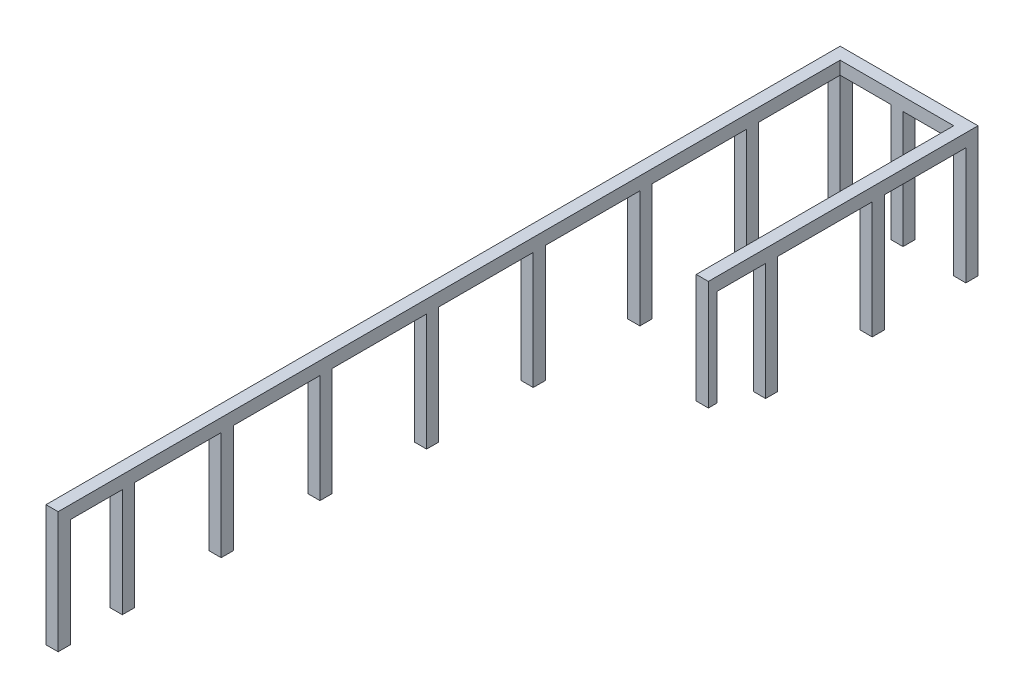
SolidWorks part; units mm, degrees
ref_plane "前视基准面" through (0, 0, 0) normal (0, 0, 1) x (1, 0, 0)
ref_plane "上视基准面" through (0, 0, 0) normal (0, 1, 0) x (1, 0, 0)
ref_plane "右视基准面" through (0, 0, 0) normal (1, 0, 0) x (0, 0, -1)
other "Configuration Table"
sketch "草图1" plane through (0, 0, 0) normal (0, 1, 0) x (1, 0, 0)
  line L13 (1.6, -1.6) -> (4.4, -1.6)
  line L14 (1.6, -1.6) -> (1.6, -4.4)
  line L15 (1.6, -4.4) -> (4.4, -4.4)
  line L16 (4.4, -1.6) -> (4.4, -4.4)
  line L17 (16.1, -1.6) -> (18.9, -1.6)
  line L18 (16.1, -1.6) -> (16.1, -4.4)
  line L19 (16.1, -4.4) -> (18.9, -4.4)
  line L20 (18.9, -1.6) -> (18.9, -4.4)
  line L21 (30.6, -1.6) -> (33.4, -1.6)
  line L22 (30.6, -1.6) -> (30.6, -4.4)
  line L23 (30.6, -4.4) -> (33.4, -4.4)
  line L24 (33.4, -1.6) -> (33.4, -4.4)
  line L25 (4.4, -1.6) -> (16.1, -1.6)
  line L26 (4.4, -1.6) -> (4.4, -4.4)
  line L27 (4.4, -4.4) -> (16.1, -4.4)
  line L28 (16.1, -1.6) -> (16.1, -4.4)
  line L29 (18.9, -1.6) -> (30.6, -1.6)
  line L30 (18.9, -1.6) -> (18.9, -4.4)
  line L31 (18.9, -4.4) -> (30.6, -4.4)
  line L32 (30.6, -1.6) -> (30.6, -4.4)
  line L33 (1.6, -23.2) -> (4.4, -23.2)
  line L34 (1.6, -23.2) -> (1.6, -26)
  line L35 (1.6, -26) -> (4.4, -26)
  line L36 (4.4, -23.2) -> (4.4, -26)
  line L37 (1.6, -47.8) -> (4.4, -47.8)
  line L38 (1.6, -47.8) -> (1.6, -50.6)
  line L39 (1.6, -50.6) -> (4.4, -50.6)
  line L40 (4.4, -47.8) -> (4.4, -50.6)
  line L41 (1.6, -72.4) -> (4.4, -72.4)
  line L42 (1.6, -72.4) -> (1.6, -75.2)
  line L43 (1.6, -75.2) -> (4.4, -75.2)
  line L44 (4.4, -72.4) -> (4.4, -75.2)
  line L45 (1.6, -97) -> (4.4, -97)
  line L46 (1.6, -97) -> (1.6, -99.8)
  line L47 (1.6, -99.8) -> (4.4, -99.8)
  line L48 (4.4, -97) -> (4.4, -99.8)
  line L53 (30.6, -47.8) -> (33.4, -47.8)
  line L54 (30.6, -47.8) -> (30.6, -50.6)
  line L55 (30.6, -50.6) -> (33.4, -50.6)
  line L56 (33.4, -47.8) -> (33.4, -50.6)
  line L57 (30.6, -23.2) -> (33.4, -23.2)
  line L58 (30.6, -23.2) -> (30.6, -26)
  line L59 (30.6, -26) -> (33.4, -26)
  line L60 (33.4, -23.2) -> (33.4, -26)
  line L61 (1.6, -4.4) -> (4.4, -4.4)
  line L62 (1.6, -4.4) -> (1.6, -23.2)
  line L63 (1.6, -23.2) -> (4.4, -23.2)
  line L64 (4.4, -4.4) -> (4.4, -23.2)
  line L65 (1.6, -26) -> (4.4, -26)
  line L66 (1.6, -26) -> (1.6, -47.8)
  line L67 (1.6, -47.8) -> (4.4, -47.8)
  line L68 (4.4, -26) -> (4.4, -47.8)
  line L69 (4.4, -72.4) -> (1.6, -72.4)
  line L70 (4.4, -72.4) -> (4.4, -50.6)
  line L71 (4.4, -50.6) -> (1.6, -50.6)
  line L72 (1.6, -72.4) -> (1.6, -50.6)
  line L73 (1.6, -75.2) -> (4.4, -75.2)
  line L74 (1.6, -75.2) -> (1.6, -97)
  line L75 (1.6, -97) -> (4.4, -97)
  line L76 (4.4, -75.2) -> (4.4, -97)
  line L77 (1.6, -99.8) -> (4.4, -99.8)
  line L78 (1.6, -99.8) -> (1.6, -121.6)
  line L79 (1.6, -121.6) -> (4.4, -121.6)
  line L80 (4.4, -99.8) -> (4.4, -121.6)
  line L81 (1.6, -121.6) -> (4.4, -121.6)
  line L82 (1.6, -121.6) -> (1.6, -124.4)
  line L83 (1.6, -124.4) -> (4.4, -124.4)
  line L84 (4.4, -121.6) -> (4.4, -124.4)
  line L85 (1.6, -124.4) -> (4.4, -124.4)
  line L86 (1.6, -124.4) -> (1.6, -144.4)
  line L87 (1.6, -144.4) -> (4.4, -144.4)
  line L88 (4.4, -124.4) -> (4.4, -144.4)
  line L89 (4.4, -144.4) -> (1.6, -144.4)
  line L90 (4.4, -144.4) -> (4.4, -147.2)
  line L91 (4.4, -147.2) -> (1.6, -147.2)
  line L92 (1.6, -144.4) -> (1.6, -147.2)
  line L93 (1.6, -147.2) -> (4.4, -147.2)
  line L94 (1.6, -147.2) -> (1.6, -167.2)
  line L95 (1.6, -167.2) -> (4.4, -167.2)
  line L96 (4.4, -147.2) -> (4.4, -167.2)
  line L97 (4.4, -167.2) -> (1.6, -167.2)
  line L98 (4.4, -167.2) -> (4.4, -170)
  line L99 (4.4, -170) -> (1.6, -170)
  line L100 (1.6, -167.2) -> (1.6, -170)
  line L101 (1.6, -170) -> (4.4, -170)
  line L102 (1.6, -170) -> (1.6, -182)
  line L103 (1.6, -182) -> (4.4, -182)
  line L104 (4.4, -170) -> (4.4, -182)
  line L105 (1.6, -182) -> (4.4, -182)
  line L106 (1.6, -182) -> (1.6, -184.8)
  line L107 (1.6, -184.8) -> (4.4, -184.8)
  line L108 (4.4, -182) -> (4.4, -184.8)
  line L109 (30.6, -4.4) -> (33.4, -4.4)
  line L110 (30.6, -4.4) -> (30.6, -23.2)
  line L111 (30.6, -23.2) -> (33.4, -23.2)
  line L112 (33.4, -4.4) -> (33.4, -23.2)
  line L113 (33.4, -26) -> (30.6, -26)
  line L114 (33.4, -26) -> (33.4, -47.8)
  line L115 (33.4, -47.8) -> (30.6, -47.8)
  line L116 (30.6, -26) -> (30.6, -47.8)
  point P50 (3, -72.4)
  dimension "D3" = 1.6
  dimension "D4" = 11.7
  dimension "D5" = 11.7
  dimension "D1" = 2.8
  dimension "D2" = 1.6
  dimension "D6" = 18.8
  dimension "D7" = 21.8
  dimension "D8" = 21.8
  dimension "D9" = 21.8
  dimension "D10" = 21.8
  dimension "D11" = 20
  dimension "D12" = 20
  dimension "D13" = 12
extrude "凸台-拉伸1" add sketch "草图1" along normal blind 30 contours L108 L103 L106 L107 | L95 L100 L99 L98 | L87 L92 L91 L90 | L84 L79 L82 L83 | L48 L45 L46 L47 | L44 L41 L42 L43 | L40 L37 L38 L39 | L56 L53 L54 L55 | L60 L57 L58 L59 | L36 L33 L34 L35 | L24 L21 L22 L23 | L20 L17 L18 L19 | L16 L13 L14 L15
extrude "凸台-拉伸2" add sketch "草图1<6>" against normal blind 3 from surface contours L108 | L104 L99 L102 L103 | L96 L91 L94 L95 | L88 L83 L86 L87 | L80 L47 L78 L79 | L76 L43 L74 L45 | L72 L41 L70 L39 | L68 L35 L66 L37 | L64 L15 L62 L33 | L16 L27 L18 L25 | L20 L31 L22 L29 | L112 L23 L110 L57 | L59 L116 L53 L114 | L55 region at (10.25, 0, 3) region at (3, 0, 13.8) region at (24.75, 0, 3) region at (3, 0, 36.9) region at (32, 0, 13.8) region at (3, 0, 61.5) region at (32, 0, 36.9) region at (3, 0, 86.1) region at (3, 0, 110.7) region at (3, 0, 134.4) region at (3, 0, 157.2) region at (3, 0, 176) starting at face at (3, 30, 49.2)
sketch "草图1<6>" plane through (0, 0, 0) normal (0, 1, 0) x (1, 0, 0) same geometry as "草图1"
sketch "草图2" plane through (1.6, 0, 0) normal (-1, 0, 0) x (0, 0, 1)
  line L0 (184.8, 30) -> (184.8, 0) construction
  line L1 (184.8, 0) -> (121.6, 0)
  line L2 (184.8, 0) -> (184.8, 2)
  line L3 (184.8, 2) -> (121.6, 2)
  line L4 (121.6, 0) -> (121.6, 2)
  line L5 (121.6, 27) -> (121.6, 0) construction
  line L6 (121.6, 0) -> (124.4, 0) construction
  dimension "D1" = 2
extrude "切除-拉伸1" cut sketch "草图2" against normal through all
sketch "草图3" plane through (33.4, 0, 0) normal (1, 0, 0) x (0, 0, -1)
  line L0 (-4.4, 30) -> (-184.8, 30) construction
  line L1 (-61.8, 4.7) -> (-63.8, 4.7)
  line L2 (-61.8, 4.7) -> (-61.8, 30)
  line L3 (-61.8, 30) -> (-63.8, 30)
  line L4 (-63.8, 4.7) -> (-63.8, 30)
  line L5 (-50.6, 27) -> (-72.4, 27) construction
  line L6 (-61.8, 30) -> (-50.6, 30)
  line L7 (-61.8, 30) -> (-61.8, 27)
  line L8 (-61.8, 27) -> (-50.6, 27)
  line L9 (-50.6, 30) -> (-50.6, 27)
  line L10 (-50.6, 30) -> (-50.6, 0) construction
  point P13 (-61.8, 4.5)
  dimension "D1" = 2
  dimension "D2" = 11.2
  dimension "D3" = 25.3
extrude "凸台-拉伸3" add sketch "草图3" against normal up to surface (2.8 mm away) contours L6 L9 L8 L7 | L3 L4 L1 L2 up to face at (30.6, 16.8, 30.4)
